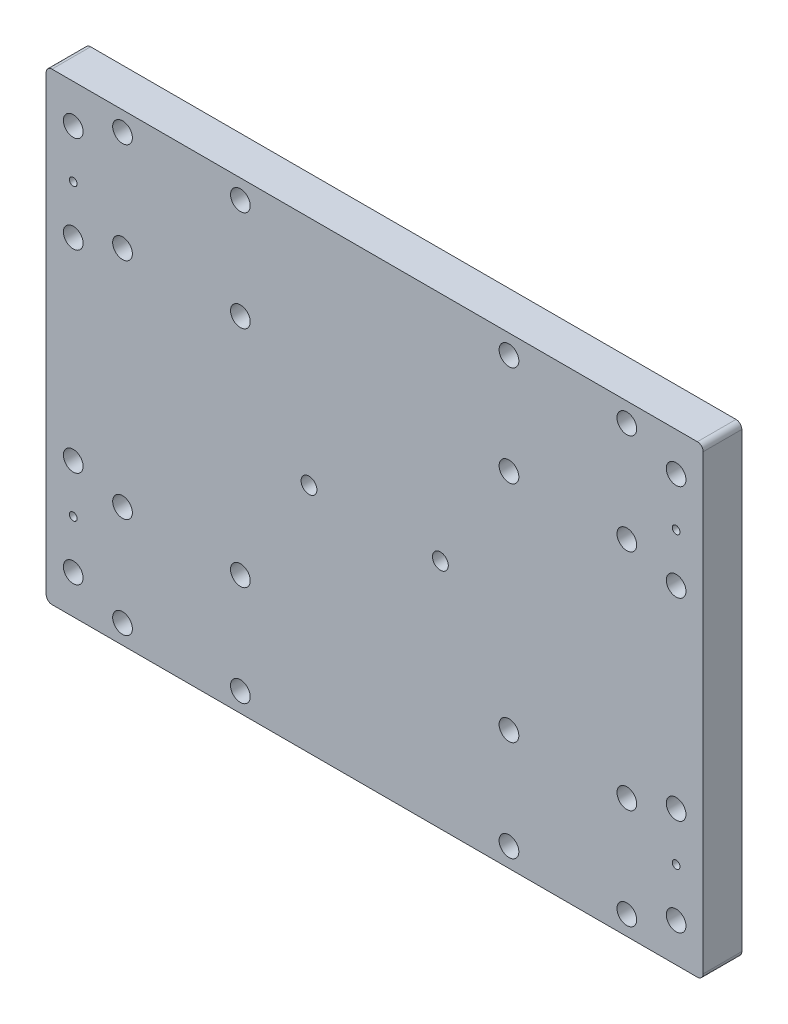
SolidWorks part; units mm, degrees
ref_plane "Front Plane" through (0, 0, 0) normal (0, 0, 1) x (1, 0, 0)
ref_plane "Top Plane" through (0, 0, 0) normal (0, 1, 0) x (1, 0, 0)
ref_plane "Right Plane" through (0, 0, 0) normal (1, 0, 0) x (0, 0, -1)
sketch "Sketch1" plane through (0, 0, 0) normal (0, 0, 1) x (1, 0, 0)
  line L1 (85, -60) -> (-85, -60)
  line L2 (85, -60) -> (85, 60)
  line L3 (85, 60) -> (-85, 60)
  line L4 (-85, -60) -> (-85, 60)
  line L5 (85, -60) -> (-85, 60) construction
  line L6 (85, 60) -> (-85, -60) construction
  point P0 (0, 0)
  dimension "D1" = 170
  dimension "D2" = 120
extrude "Boss-Extrude1" add sketch "Sketch1" along normal mid plane 10
sketch "Sketch2" plane through (0, 0, 5) normal (0, 0, 1) x (1, 0, 0)
  line L0 (-65.25, 71) -> (-65.25, -71) construction
  line L1 (65.25, -71) -> (65.25, 71) construction
  line L2 (-34.75, 71) -> (-34.75, -71) construction
  line L3 (34.75, -71) -> (34.75, 71) construction
  line L4 (70.6711, 55) -> (-71.3289, 55) construction
  line L5 (-71.3289, -55) -> (70.6711, -55) construction
  line L6 (70.6711, 29) -> (-71.3289, 29) construction
  line L7 (-71.3289, -29) -> (70.6711, -29) construction
  line L8 (85, 60) -> (-85, 60) construction
  line L9 (-85, -60) -> (85, -60) construction
  line L10 (-85, 60) -> (-85, -60) construction
  line L11 (85, -60) -> (85, 60) construction
  circle A0 centre (-65.25, 55) radius 2.55
  circle A1 centre (-34.75, 55) radius 2.55
  circle A2 centre (-34.75, 29) radius 2.55
  circle A3 centre (-65.25, 29) radius 2.55
  circle A4 centre (65.25, 55) radius 2.55
  circle A5 centre (65.25, 29) radius 2.55
  circle A6 centre (34.75, 29) radius 2.55
  circle A7 centre (34.75, 55) radius 2.55
  circle A8 centre (-65.25, -29) radius 2.55
  circle A9 centre (-34.75, -29) radius 2.55
  circle A10 centre (-34.75, -55) radius 2.55
  circle A11 centre (-65.25, -55) radius 2.55
  circle A12 centre (34.75, -29) radius 2.55
  circle A13 centre (65.25, -29) radius 2.55
  circle A14 centre (65.25, -55) radius 2.55
  circle A15 centre (34.75, -55) radius 2.55
  dimension "D1" = 5.1
  dimension "D2" = 5.1
  dimension "D3" = 5.1
  dimension "D4" = 5.1
  dimension "D5" = 5.1
  dimension "D6" = 5.1
  dimension "D7" = 5.1
  dimension "D8" = 5.1
  dimension "D9" = 5.1
  dimension "D10" = 5.1
  dimension "D11" = 5.1
  dimension "D12" = 5.1
  dimension "D13" = 5.1
  dimension "D14" = 5.1
  dimension "D15" = 5.1
  dimension "D16" = 5.1
  dimension "D17" = 5
  dimension "D18" = 5
  dimension "D19" = 26
  dimension "D20" = 26
  dimension "D21" = 30.5
  dimension "D22" = 30.5
  dimension "D23" = 19.75
  dimension "D24" = 19.75
extrude "Cut-Extrude1" cut sketch "Sketch2" against normal through all
sketch "Sketch4" plane through (0, 0, 5) normal (0, 0, 1) x (1, 0, 0)
  line L3 (-17, 0) -> (17, 0) construction
  circle A0 centre (-17, 0) radius 2.05
  circle A3 centre (17, 0) radius 2.05
  point P0 (0, 0)
  dimension "D3" = 4.1
  dimension "D4" = 4.1
  dimension "D1" = 34
extrude "Cut-Extrude3" cut sketch "Sketch4" against normal through all
fillet "Fillet1" radius 1.5 4 edges at (-85, -60, 0) (85, -60, 0) (85, 60, 0) (-85, 60, 0)
sketch "Sketch6" plane through (0, 0, 5) normal (0, 0, 1) x (1, 0, 0)
  line L0 (-78, -1002.1032) -> (-78, 48997.8968) construction
  line L1 (78, -1010.3548) -> (78, 48989.6452) construction
  line L2 (-85, 58.5) -> (-85, -58.5) construction
  line L3 (85, -58.5) -> (85, 58.5) construction
  line L4 (83.5, 60) -> (-83.5, 60) construction
  line L5 (-83.5, -60) -> (83.5, -60) construction
  circle A0 centre (-78, 50) radius 2.55
  circle A1 centre (-78, 37.5) radius 1
  circle A2 centre (-78, 25) radius 2.55
  circle A3 centre (-78, -25) radius 2.55
  circle A4 centre (-78, -37.5) radius 1
  circle A5 centre (-78, -50) radius 2.55
  dimension "D3" = 5.1
  dimension "D4" = 2
  dimension "D5" = 5.1
  dimension "D6" = 5.1
  dimension "D7" = 5.1
  dimension "D8" = 2
  dimension "D9" = 10
  dimension "D12" = 35
  dimension "D14" = 10
  dimension "D1" = 7
  dimension "D2" = 7
  dimension "D10" = 22.5
  dimension "D11" = 35
  dimension "D13" = 22.5
extrude "Cut-Extrude5" cut sketch "Sketch6" against normal through all
mirror "Mirror1" about plane through (0, 0, 0) normal (1, 0, 0) of "Cut-Extrude5"
equation "\"D23@Sketch2\"=5.75+14"
equation "\"D24@Sketch2\"=5.75+14"
equation "\"D4@Sketch4\"=\"D3@Sketch4\""
equation "\"D5@Sketch6\" = \"D3@Sketch6\""
equation "\"D6@Sketch6\" = \"D3@Sketch6\""
equation "\"D7@Sketch6\"=\"D3@Sketch6\""
